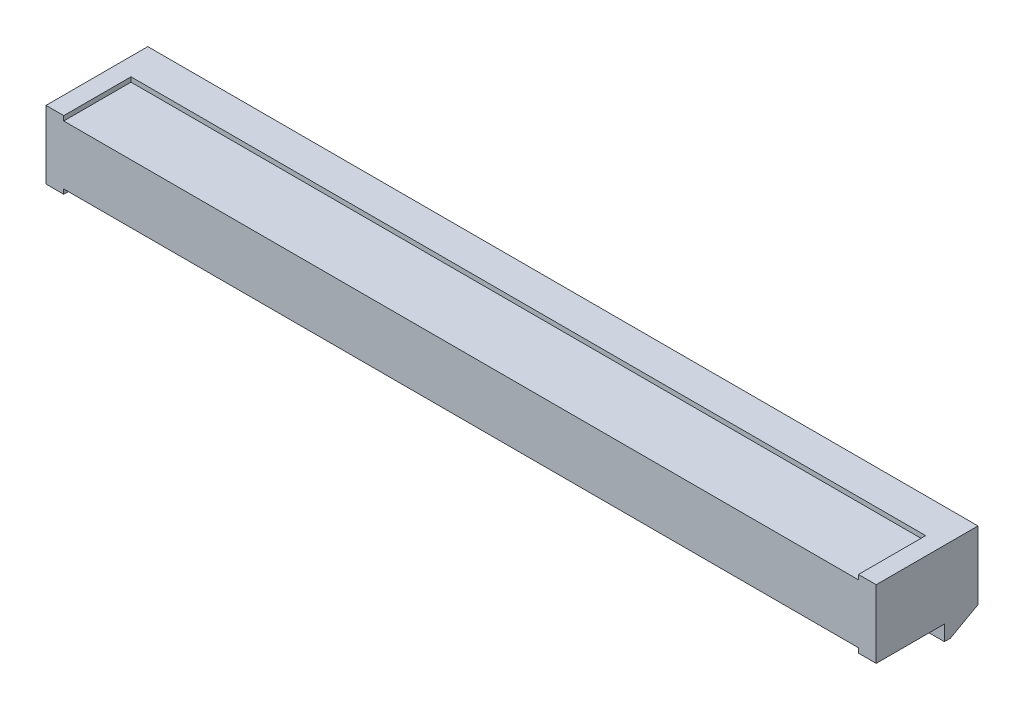
SolidWorks part; units mm, degrees
ref_plane "Front" through (0, 0, 0) normal (0, 0, 1) x (1, 0, 0)
ref_plane "Top" through (0, 0, 0) normal (0, 1, 0) x (1, 0, 0)
ref_plane "Right" through (0, 0, 0) normal (1, 0, 0) x (0, 0, -1)
sketch "Sketch1" plane through (0, 0, 0) normal (0, 1, 0) x (1, 0, 0)
  line L1 (-44.45, -5.45) -> (44.45, -5.45)
  line L2 (-44.45, -5.45) -> (-44.45, 5.45)
  line L3 (-44.45, 5.45) -> (44.45, 5.45)
  line L4 (44.45, -5.45) -> (44.45, 5.45)
  line L5 (-44.45, -5.45) -> (44.45, 5.45) construction
  line L6 (-44.45, 5.45) -> (44.45, -5.45) construction
  point P0 (0, 0)
  dimension "D1" = 88.9
  dimension "D2" = 10.9
extrude "Boss-Extrude1" add sketch "Sketch1" along normal blind 3.65
sketch "Sketch2" plane through (0, 3.65, 0) normal (0, 1, 0) x (1, 0, 0)
  line L0 (-44.45, -5.45) -> (44.45, -5.45) construction
  line L1 (-42.55, -5.45) -> (42.55, -5.45)
  line L2 (-42.55, -5.45) -> (-42.55, 1.75)
  line L3 (-42.55, 1.75) -> (42.55, 1.75)
  line L4 (42.55, -5.45) -> (42.55, 1.75)
  line L5 (-44.45, 5.45) -> (-44.45, -5.45) construction
  line L6 (44.45, -5.45) -> (44.45, 5.45) construction
  line L7 (44.45, 5.45) -> (-44.45, 5.45) construction
  dimension "D1" = 1.9
  dimension "D2" = 1.9
  dimension "D3" = 3.7
extrude "Cut-Extrude1" cut sketch "Sketch2" against normal blind 0.5
sketch "Sketch3" plane through (0, 0, -5.45) normal (0, 0, -1) x (-1, 0, 0)
  line L0 (-44.45, 0) -> (44.45, 0) construction
  line L1 (-42.55, 0) -> (-30.85, 0)
  line L2 (-42.55, 0) -> (-42.55, 0.85)
  line L3 (-42.55, 0.85) -> (-30.85, 0.85)
  line L4 (-30.85, 0) -> (-30.85, 0.85)
  line L5 (-44.45, 3.65) -> (-44.45, 0) construction
  line L6 (-29.15, 0) -> (42.55, 0)
  line L7 (-29.15, 0) -> (-29.15, 0.85)
  line L8 (-29.15, 0.85) -> (42.55, 0.85)
  line L9 (42.55, 0) -> (42.55, 0.85)
  line L10 (44.45, 3.65) -> (44.45, 0) construction
  dimension "D1" = 0.85
  dimension "D2" = 1.9
  dimension "D3" = 1.9
  dimension "D4" = 11.7
  dimension "D5" = 1.7
extrude "Cut-Extrude2" cut sketch "Sketch3" against normal blind 7.82
chamfer "Chamfer1" distance 0.3 angle 45 2 edges at (29.15, 0.425, -5.45) (30.85, 0.425, -5.45)
sketch "Sketch4" plane through (0, 0, -5.45) normal (0, 0, -1) x (-1, 0, 0)
  line L0 (-44.45, 3.65) -> (44.45, 3.65) construction
  line L1 (-43.61, 2.88) -> (-42.41, 2.88)
  line L2 (-43.61, 2.88) -> (-43.61, 1.68)
  line L3 (-43.61, 1.68) -> (-42.41, 1.68)
  line L4 (-42.41, 2.88) -> (-42.41, 1.68)
  line L5 (-44.45, 3.65) -> (-44.45, 0) construction
  line L6 (-30, 0) -> (-30, 3.65) construction
  line L7 (-30.55, 0) -> (-29.45, 0) construction
  line L8 (-42.41, 2.28) -> (44.45, 2.28) construction
  line L9 (44.45, 3.65) -> (44.45, 0) construction
  line L10 (0, 3.65) -> (0, 0) construction
  line L11 (-30.6, 2.88) -> (-29.4, 2.88)
  line L12 (-30.6, 2.88) -> (-30.6, 1.68)
  line L13 (-30.6, 1.68) -> (-29.4, 1.68)
  line L14 (-29.4, 2.88) -> (-29.4, 1.68)
  line L15 (-30.6, 2.88) -> (-29.4, 1.68) construction
  line L16 (-30.6, 1.68) -> (-29.4, 2.88) construction
  line L17 (42.41, 2.88) -> (42.41, 1.68)
  line L18 (43.61, 1.68) -> (42.41, 1.68)
  line L19 (43.61, 2.88) -> (43.61, 1.68)
  line L20 (43.61, 2.88) -> (42.41, 2.88)
  point P16 (-30, 2.28)
  dimension "D1" = 1.2
  dimension "D2" = 0.77
  dimension "D3" = 0.84
extrude "Cut-Extrude3" cut sketch "Sketch4" against normal blind 7.82
sketch "Sketch5" plane through (0, 0, -5.45) normal (0, 0, -1) x (-1, 0, 0)
  line L0 (-44.45, 3.65) -> (44.45, 3.65) construction
  line L1 (-41.91, 2.91) -> (-41.41, 2.91)
  line L2 (-41.91, 2.91) -> (-41.91, 1.54)
  line L3 (-41.91, 1.54) -> (-41.41, 1.54)
  line L4 (-41.41, 2.91) -> (-41.41, 1.54)
  line L5 (-44.45, 3.65) -> (-44.45, 0) construction
  dimension "D1" = 0.74
  dimension "D2" = 1.37
  dimension "D3" = 0.5
  dimension "D4" = 2.54
extrude "Cut-Extrude4" cut sketch "Sketch5" against normal blind 7.82
pattern_linear "LPattern1" count 84 spacing 1 along (-1, 0, 0) skipping (11, 0), (12, 0) of "Cut-Extrude4"
mirror "Mirror1" about plane through (0, 0, 0) normal (0, -1, 0) of bodies 106
sketch "Sketch6" plane through (44.45, 0, 0) normal (1, 0, 0) x (0, 0, -1)
  line L0 (5.45, -3.65) -> (2.5026, -5.2875)
  line L1 (1.85, -5.2875) -> (1.85, -3.65)
  line L2 (-5.45, -3.65) -> (5.45, -3.65) construction
  line L3 (1.85, -3.65) -> (5.45, -3.65)
  line L4 (1.85, -5.2875) -> (2.5026, -5.2875)
  dimension "D1" = 3.6
extrude "Boss-Extrude2" add sketch "Sketch6" against normal up to surface (88.9 mm away) up to face at (-44.45, 0, 0)
sketch "Sketch7" plane through (0, 0, -5.45) normal (0, 0, -1) x (-1, 0, 0)
  line L0 (-44.45, -3.65) -> (44.45, -3.65) construction
  line L1 (-40.45, -3.65) -> (-39.18, -3.65)
  line L2 (-40.45, -3.65) -> (-40.45, -5.2875)
  line L3 (-40.45, -5.2875) -> (-39.18, -5.2875)
  line L4 (-39.18, -3.65) -> (-39.18, -5.2875)
  line L5 (44.45, -5.2875) -> (-44.45, -5.2875) construction
  line L6 (-44.45, -5.2875) -> (-44.45, -3.65) construction
  dimension "D1" = 4
  dimension "D2" = 1.27
extrude "Cut-Extrude5" cut sketch "Sketch7" against normal through all
pattern_linear "LPattern3" count 17 spacing 5 along (-1, 0, 0) of "Cut-Extrude5"
ref_plane "Plane1" through (0, 0, 1.862) normal (0, 0, -1) x (-1, 0, 0)
ref_plane "Plane2" through (0, 0, 0) normal (-1, 0, 0) x (0, 0, 1)
